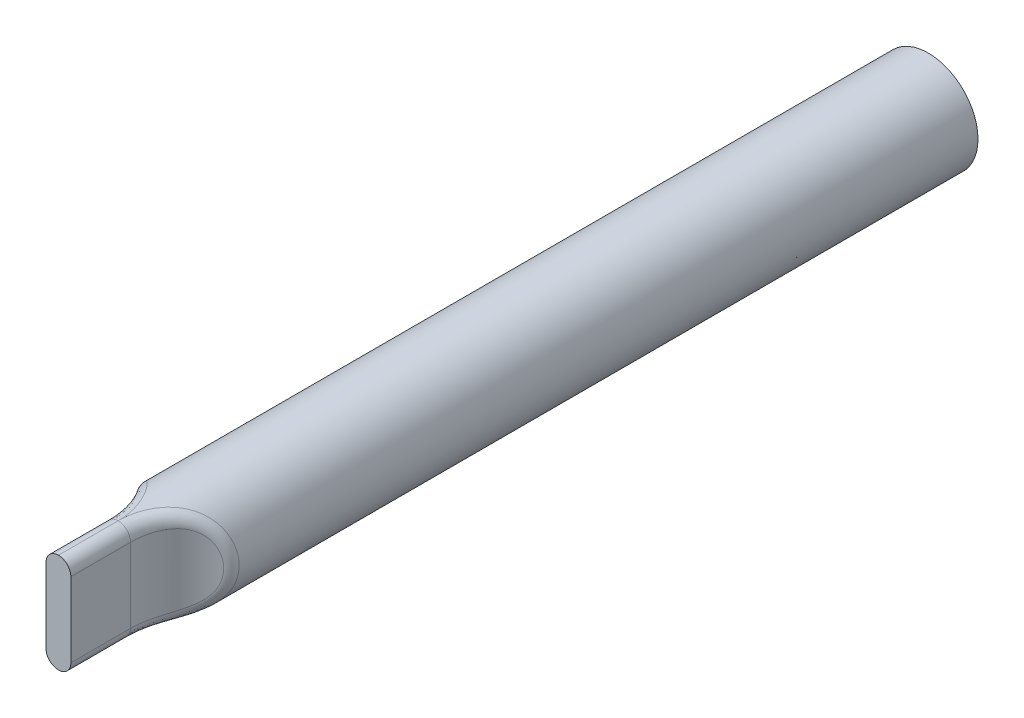
SolidWorks part; units mm, degrees
ref_plane "Front Plane" through (0, 0, 0) normal (0, 0, 1) x (1, 0, 0)
ref_plane "Top Plane" through (0, 0, 0) normal (0, 1, 0) x (1, 0, 0)
ref_plane "Right Plane" through (0, 0, 0) normal (1, 0, 0) x (0, 0, -1)
sketch "Sketch1" plane through (0, 0, 0) normal (0, 0, 1) x (1, 0, 0)
  circle A0 centre (0, 0) radius 2
  dimension "D1" = 4
extrude "Boss-Extrude1" add sketch "Sketch1" along normal blind 35
sketch "Sketch2" plane through (0, 0, 0) normal (0, 1, 0) x (1, 0, 0)
  line L0 (0, -35) -> (0, -25.1492) construction
  line L1 (-2, -35) -> (2, -35) construction
  line L2 (-0.5, -35) -> (-0.5, -32.5981)
  line L3 (-2, 0) -> (-2, -35) construction
  line L4 (-2, -30) -> (-2, -35)
  line L5 (-2, -35) -> (-0.5, -35)
  line L6 (2, -35) -> (0.5, -35)
  line L7 (2, -30) -> (2, -35)
  line L8 (0.5, -35) -> (0.5, -32.5981)
  arc A0 (-0.5, -32.5981) -> (-2, -30) centre (-3.5, -32.5981) ccw
  arc A1 (0.5, -32.5981) -> (2, -30) centre (3.5, -32.5981) cw
  dimension "D2" = 3
  dimension "D1" = 1
  dimension "D3" = 5
extrude "Cut-Extrude1" cut sketch "Sketch2" against normal through all both and the other way through all
fillet "Fillet1" radius 0.5 6 edges at (0.5, -1.9365, 33.799) (1.9982, -0.0842, 30.001) (-0.5, -1.9365, 33.799) (-0.5, 1.9365, 33.799) (0.5, 1.9365, 33.799) (-1.9982, 0.0842, 30.001)
shell "Shell1" thickness 0.25 removed face at (2, 0, 0)
sketch "Sketch3" plane through (0, 0, 0) normal (0, 1, 0) x (1, 0, 0)
  line L0 (0, 0) -> (0, -14) construction
  line L1 (0, -14) -> (0, -19) construction
  line L2 (0, -19) -> (0, -24) construction
  circle A0 centre (0, -24) radius 1
  circle A1 centre (0, -19) radius 1
  circle A2 centre (0, -14) radius 1
  dimension "D1" = 2
  dimension "D2" = 5
  dimension "D3" = 14
extrude "Cut-Extrude2" cut sketch "Sketch3" against normal blind 30
sketch "Sketch4" plane through (0, 0, 0) normal (0, 1, 0) x (0, 0, -1)
  line L0 (8, 20) -> (8, 8)
  arc A0 (8, 8) -> (0, 0) centre (0, 8) cw
  dimension "D2" = 8
  dimension "D1" = 20
sweep "Sweep-Thin1" [suppressed] add path "Sketch4" circular profile diameter 4 parameters "D1"=0.25, "D3"=4
sketch "Sketch5" plane through (0, 0, 35) normal (0, 0, 1) x (1, 0, 0)
  line L0 (0, 0) -> (0, -23)
  dimension "D1" = 23
